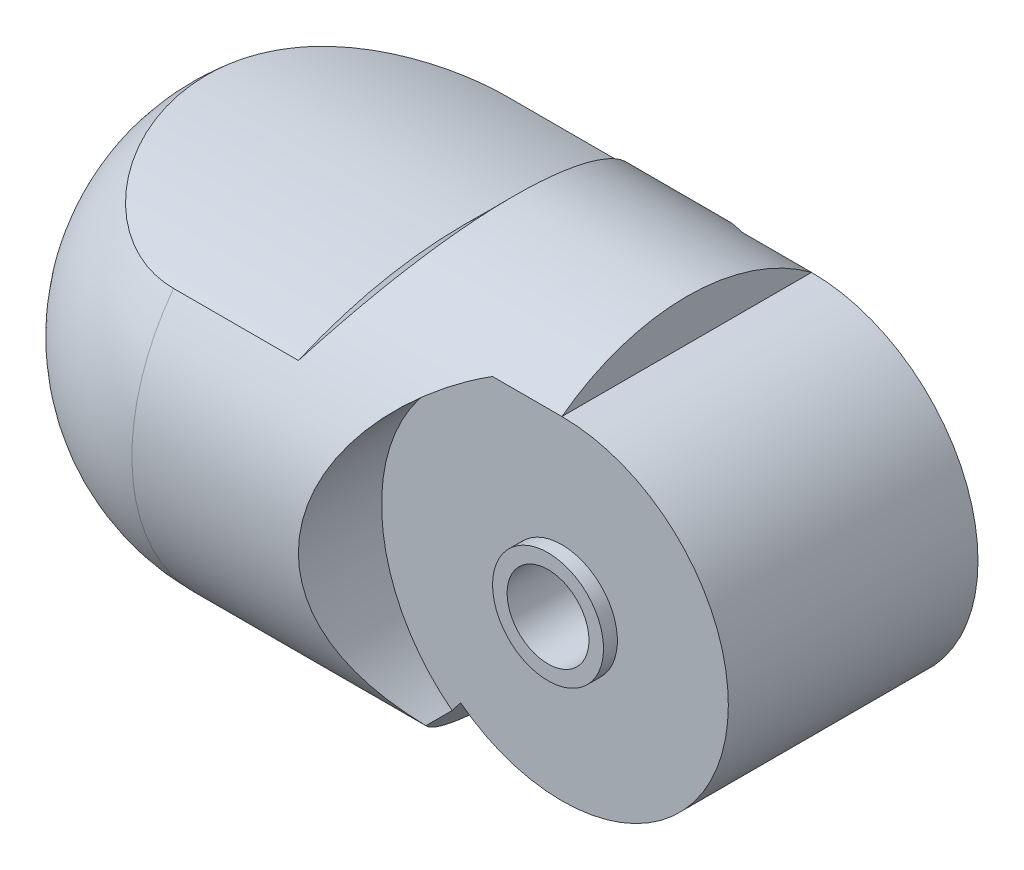
SolidWorks part; units mm, degrees
ref_plane "Front Plane" through (0, 0, 0) normal (0, 0, 1) x (1, 0, 0)
ref_plane "Top Plane" through (0, 0, 0) normal (0, 1, 0) x (1, 0, 0)
ref_plane "Right Plane" through (0, 0, 0) normal (1, 0, 0) x (0, 0, -1)
sketch "Sketch1" plane through (0, 0, 0) normal (0, 0, 1) x (1, 0, 0)
  circle A0 centre (0, 0) radius 1.475
  circle A1 centre (0, 0) radius 6
  dimension "D1" = 2.95
  dimension "D2" = 12
extrude "Boss-Extrude1" add sketch "Sketch1" along normal mid plane 9
sketch "Sketch5" plane through (0, 0, 0) normal (0, 0, 1) x (1, 0, 0)
  line L0 (-26.6252, 0) -> (14.5008, 0) construction
  line L1 (0, -7.5) -> (-12.5, -7.5)
  line L3 (0, 0) -> (0, -7.5)
  line L4 (-20, 0) -> (0, 0)
  arc A0 (-12.5, -7.5) -> (-20, 0) centre (-12.5, 0) cw
  dimension "D1" = 15
  dimension "D2" = 20
revolve "Revolve1" add sketch "Sketch5" angle 360 about L0
sketch "Sketch7" plane through (0, 0, 0) normal (0, 0, 1) x (1, 0, 0)
  line L0 (-3.6526, -4.7601) -> (-5.755, -7.5)
  line L1 (-12.5, -7.5) -> (0, -7.5) construction
  line L2 (-5.755, -7.5) -> (0, -7.5)
  line L3 (0, -7.5) -> (0, -6)
  arc A0 (0, -6) -> (-3.6526, -4.7601) centre (0, 0) ccw
  circle A1 centre (0, 0) radius 6 construction
  dimension "D2" = 6
  dimension "D1" = 37.5
extrude "Cut-Extrude2" cut sketch "Sketch7" against normal through all both and the other way through all
combine bodies "Combine1" operation type add bodies to combine 101 105
sketch "Sketch6" plane through (0, 0, 0) normal (1, 0, 0) x (0, 0, -1)
  arc A0 (-6, 4.5) -> (6, 4.5) centre (0, -9.2477) cw
  circle A1 centre (0, 0) radius 7.5 construction
  arc A2 (-6, 4.5) -> (6, 4.5) centre (0, 0) cw
  point P3 (0, 5.7523)
  dimension "D2" = 15
  dimension "D1" = 12
extrude "Cut-Extrude1" cut sketch "Sketch6" against normal through all from offset 6 offset against normal yes
chamfer "Chamfer1" distance 2 angle 45 1 edges at (-6, 5.7523, 0)
sketch "Sketch9" plane through (0, 0, 0) normal (0, 0, 1) x (1, 0, 0)
  circle A0 centre (0, 0) radius 6.5
  circle A1 centre (0, 0) radius 6 construction
  dimension "D1" = 0.5
extrude "Cut-Extrude3" cut sketch "Sketch9" along normal through all from surface starting at face at (0, 0, 4.5)
extrude "Cut-Extrude4" cut sketch "Sketch9<2>" against normal through all from surface starting at face at (0, 0, -4.5)
sketch "Sketch9<2>" plane through (0, 0, 0) normal (0, 0, 1) x (1, 0, 0) same geometry as "Sketch9"
sketch "Sketch10" plane through (0, 0, 0) normal (0, 1, 0) x (1, 0, 0)
  line L0 (6, 4.5) -> (-3.6526, 4.5) construction
  line L1 (1.475, 4.5) -> (2, 4.5)
  line L2 (1.475, 4.5) -> (1.475, 5)
  line L3 (1.475, 5) -> (2, 5)
  line L4 (2, 4.5) -> (2, 5)
  line L5 (1.475, 4.5) -> (-1.475, 4.5) construction
  line L6 (-3.6526, -4.5) -> (6, -4.5) construction
  line L7 (1.475, -4.5) -> (2, -4.5)
  line L8 (1.475, -4.5) -> (1.475, -5)
  line L9 (1.475, -5) -> (2, -5)
  line L10 (2, -4.5) -> (2, -5)
  line L11 (6, 0) -> (0, 0) construction
  line L12 (0, 4.5) -> (0, -4.5) construction
  line L13 (6, -4.5) -> (6, 4.5) construction
  point P19 (6, 0)
  point P22 (0, 0)
  point P23 (0, 0)
  point P24 (0, 0)
  dimension "D2" = 4
  dimension "D3" = 10
  dimension "D4" = 10
revolve "Revolve2" add sketch "Sketch10" angle 360 about L12
